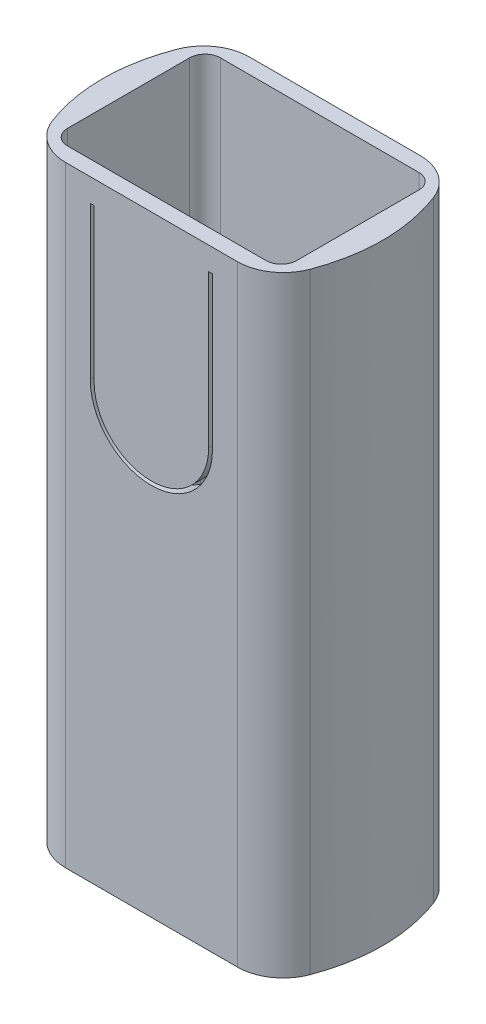
SolidWorks part; units mm, degrees
ref_plane "Front Plane" through (0, 0, 0) normal (0, 0, 1) x (1, 0, 0)
ref_plane "Top Plane" through (0, 0, 0) normal (0, 1, 0) x (1, 0, 0)
ref_plane "Right Plane" through (0, 0, 0) normal (1, 0, 0) x (0, 0, -1)
ref_plane "Plane1" through (0, 58, 0) normal (0, 1, 0) x (1, 0, 0)
sketch "Sketch8" plane through (0, 58, 0) normal (0, 1, 0) x (1, 0, 0)
  line L0 (-13, -10) -> (13, -10)
  line L1 (-15, -8) -> (-15, 8)
  line L2 (-13, 10) -> (13, 10)
  line L3 (15, -8) -> (15, 8)
  line L5 (-15, 10) -> (0, 0) construction
  line L6 (-11.243, -12) -> (11.243, -12)
  line L8 (-11.1948, 12) -> (11.1948, 12)
  line L11 (-17.3138, 11.5426) -> (-14.2911, 9.5274) construction
  line L12 (0, -12) -> (0, 12) construction
  line L15 (0, 12) -> (0, -10) construction
  line L16 (14.2911, -9.5274) -> (15, -10) construction
  line L17 (0, 0) -> (17.3138, -11.5426) construction
  line L18 (7.778, 10) -> (7.778, 12) construction
  line L19 (7.778, -10) -> (7.778, -12) construction
  arc A0 (15, -8) -> (13, -10) centre (13, -8) cw
  arc A1 (-15, -8) -> (-13, -10) centre (-13, -8) ccw
  arc A8 (-13, 10) -> (-15, 8) centre (-13, 8) ccw
  arc A9 (13, 10) -> (15, 8) centre (13, 8) cw
  arc A10 (-11.1948, 12) -> (-16.8117, 8.1097) centre (-11.1948, 6) ccw
  arc A11 (-11.243, -12) -> (-16.8596, -8.1104) centre (-11.243, -6) cw
  arc A12 (11.1948, 12) -> (16.8117, 8.1097) centre (11.1948, 6) cw
  arc A13 (11.243, -12) -> (16.8596, -8.1104) centre (11.243, -6) ccw
  spline S0 degree 3 poles (-16.8596, -8.1104) (-17.8507, -5.4727) (-18.8343, 0.0284) (-17.8195, 5.4265) (-16.8117, 8.1097) knots 0.167422 0.167422 0.167422 0.167422 0.502499 0.837905 0.837905 0.837905 0.837905
  spline S1 degree 3 poles (16.8596, -8.1104) (17.8507, -5.4727) (18.8343, 0.0284) (17.8195, 5.4265) (16.8117, 8.1097) knots 0.167422 0.167422 0.167422 0.167422 0.502499 0.837905 0.837905 0.837905 0.837905
  point P0 (0, 0)
  point P19 (-15, 10)
  point P26 (0, 0)
  point P27 (-12, 9.5)
  point P28 (15, 10)
  point P51 (-18.3347, 0)
  point P52 (18.3347, 0)
  point P53 (-15, 0)
  point P54 (15, 0)
  point P55 (0, 0)
  point P56 (0, 0)
  point P57 (0, 0)
  dimension "D3" = 2
  dimension "D6" = 16.5846
  dimension "D2" = 6
  dimension "D7" = 2
  dimension "D1" = 30
  dimension "D4" = 24
  dimension "D5" = 20
sketch "Sketch11" plane through (0, 58, 0) normal (0, 1, 0) x (1, 0, 0)
  line L10 (-13, 10) -> (13, 10) construction
  line L11 (13, 10) -> (15, 10)
  line L13 (-13, 7.4379) -> (-13, 10)
  line L14 (0, 12) -> (0, -10) construction
  line L19 (15, 10) -> (15, 6.9379)
  line L20 (15, 6.9379) -> (13.5, 6.9379)
  line L21 (13, 7.4379) -> (13, 10)
  line L22 (-15, 6.9379) -> (-13.5, 6.9379)
  line L23 (-15, 10) -> (-15, 6.9379)
  line L24 (-13, 10) -> (-15, 10)
  arc A4 (13.5, 6.9379) -> (13, 7.4379) centre (13.5, 7.4379) cw
  arc A5 (-13.5, 6.9379) -> (-13, 7.4379) centre (-13.5, 7.4379) ccw
  dimension "D1" = 0.5
extrude "Boss-Extrude4" add sketch "Sketch8" along normal blind 80
extrude "Boss-Extrude5" add sketch "Sketch11" along normal blind 57
sketch "Sketch12" plane through (0, 0, 12) normal (0, 0, 1) x (1, 0, 0)
  line L0 (0, 138) -> (0, 58) construction
  line L1 (-11.243, 138) -> (11.243, 138) construction
  line L2 (55, 58) -> (-55, 58) construction
  line L3 (0, 116.5243) -> (0, 136.5243) construction
  line L5 (7.4764, 134.9866) -> (7.4764, 114.9866)
  line L7 (-7.5236, 134.9866) -> (-7.5236, 114.9866)
  line L8 (7.4764, 134.9866) -> (7.9764, 134.9866)
  line L9 (7.9764, 134.9866) -> (7.9764, 114.9866)
  line L10 (-8.0236, 114.9866) -> (-8.0236, 134.9866)
  line L11 (-8.0236, 134.9866) -> (-7.5236, 134.9866)
  arc A0 (7.4764, 114.9866) -> (-7.5236, 114.9866) centre (-0.0236, 114.9866) cw
  arc A1 (7.9764, 114.9866) -> (-8.0236, 114.9866) centre (-0.0236, 114.9866) cw
  dimension "D3" = 0.5
  dimension "D1" = 15
  dimension "D2" = 20
  dimension "D4" = 0.5
extrude "Cut-Extrude1" cut sketch "Sketch12" against normal blind 3
